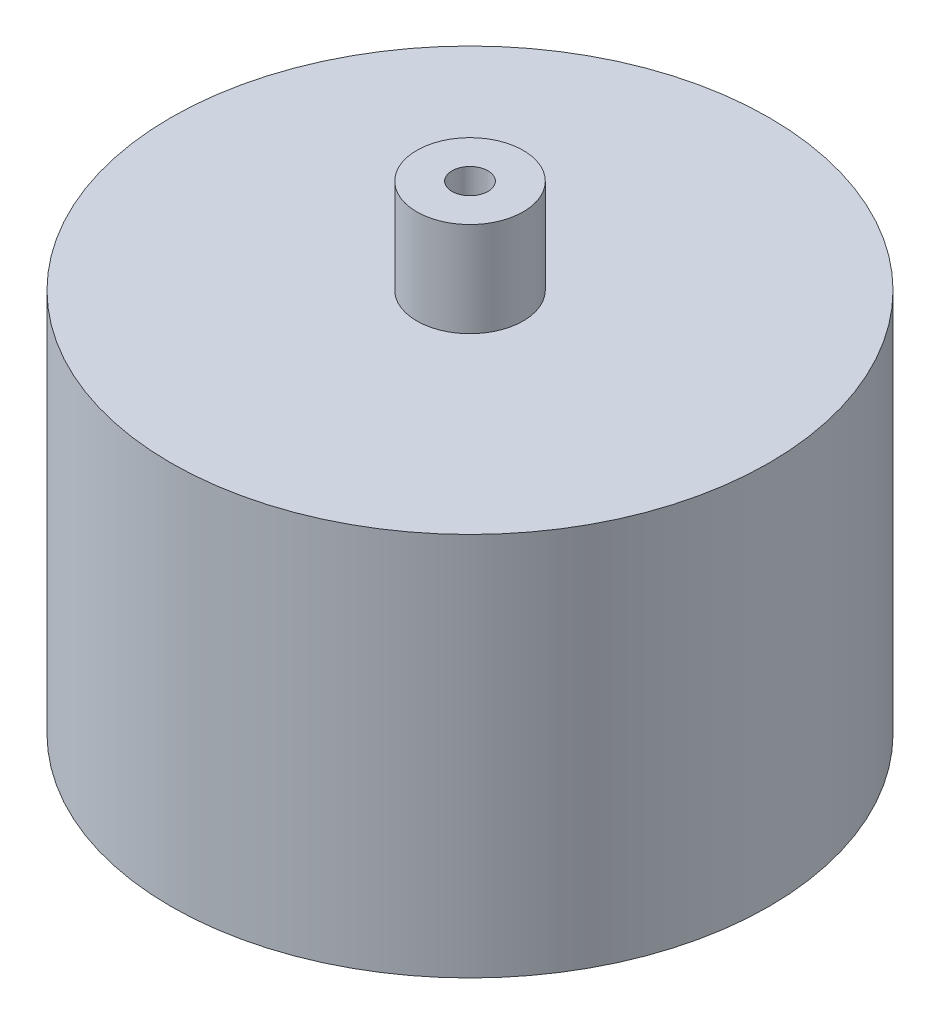
SolidWorks part; units mm, degrees
ref_plane "Front Plane" through (0, 0, 0) normal (0, 0, 1) x (1, 0, 0)
ref_plane "Top Plane" through (0, 0, 0) normal (0, 1, 0) x (1, 0, 0)
ref_plane "Right Plane" through (0, 0, 0) normal (1, 0, 0) x (0, 0, -1)
sketch "Sketch1" plane through (0, 0, 0) normal (0, 1, 0) x (1, 0, 0)
  circle A0 centre (0, 0) radius 25
  dimension "D1" = 50
extrude "Boss-Extrude1" add sketch "Sketch1" along normal blind 40
sketch "Sketch2" plane through (0, 40, 0) normal (0, 1, 0) x (1, 0, 0)
  circle A0 centre (0, 0) radius 25
  circle A1 centre (0, 0) radius 4.45
  dimension "D1" = 50
  dimension "D2" = 8.9
extrude "Cut-Extrude1" cut sketch "Sketch2" against normal blind 7.9
sketch "Sketch3" plane through (0, 40, 0) normal (0, 1, 0) x (1, 0, 0)
  circle A0 centre (0, 0) radius 1.5
  dimension "D1" = 3
extrude "Cut-Extrude2" cut sketch "Sketch3" against normal through all
